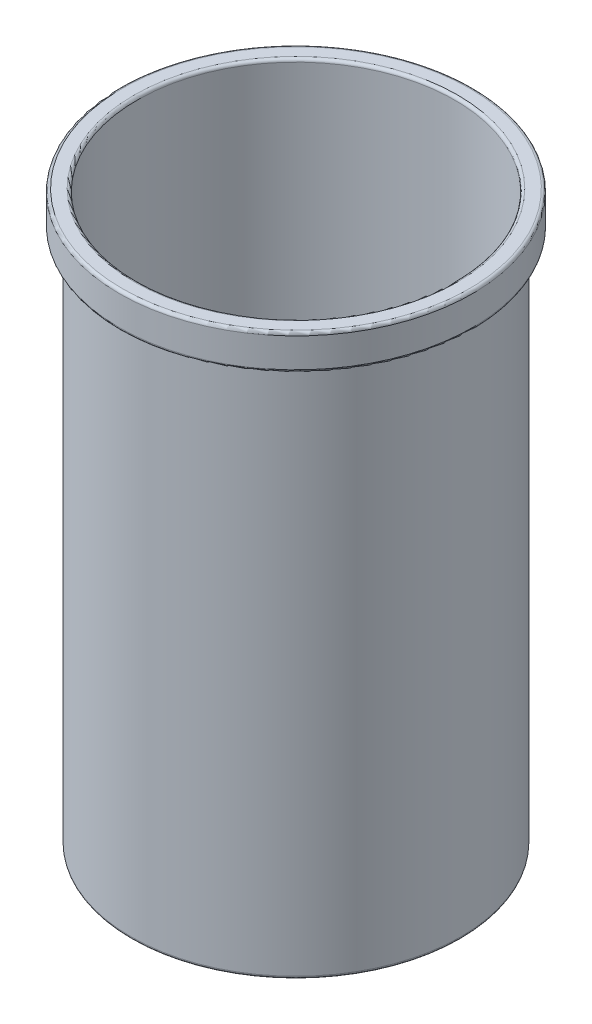
SolidWorks part; units mm, degrees
material "Cast iron, nodular graphite, EN GJS 450 10"
ref_plane "Front Plane" through (0, 0, 0) normal (0, 0, 1) x (1, 0, 0)
ref_plane "Top Plane" through (0, 0, 0) normal (0, 1, 0) x (1, 0, 0)
ref_plane "Right Plane" through (0, 0, 0) normal (1, 0, 0) x (0, 0, -1)
sketch "Sketch1" plane through (0, 0, 0) normal (0, 1, 0) x (1, 0, 0)
  circle A0 centre (0, 0) radius 56.1
  circle A1 centre (0, 0) radius 54.1
  dimension "D1" = 54.1
  dimension "D2" = 2
extrude "Boss-Extrude1" add sketch "Sketch1" along normal blind 193.66
sketch "Sketch3" plane through (0, 193.66, 0) normal (0, 1, 0) x (1, 0, 0)
  circle A0 centre (0, 0) radius 56.1 construction
  circle A1 centre (0, 0) radius 56.1
  circle A2 centre (0, 0) radius 60.1
  dimension "D1" = 4
extrude "Boss-Extrude2" add sketch "Sketch3" against normal blind 12
fillet "Fillet1" radius 1 6 edges at (0, 0, 54.1) (0, 0, 56.1) (0, 181.66, 56.1) (0, 193.66, 54.1) (0, 181.66, 60.1) (0, 193.66, 60.1)
equation "\"PS_Radius\"= 108 / 2"
equation "\"PS_Clearance\"= 0.1"
equation "\"Liner_Radius\"= \"PS_Clearance\" + \"PS_Radius\""
equation "\"D1@Sketch1\"=\"Liner_Radius\""
equation "\"Liner_Thickness\"= 2"
equation "\"D2@Sketch1\"=\"Liner_Thickness\""
equation "\"Cylinder_Length\"= 181.66 + 12"
equation "\"D1@Boss-Extrude1\"=\"Cylinder_Length\""
equation "\"Lip_Height\"= 12"
equation "\"D1@Boss-Extrude2\"=\"Lip_Height\""
